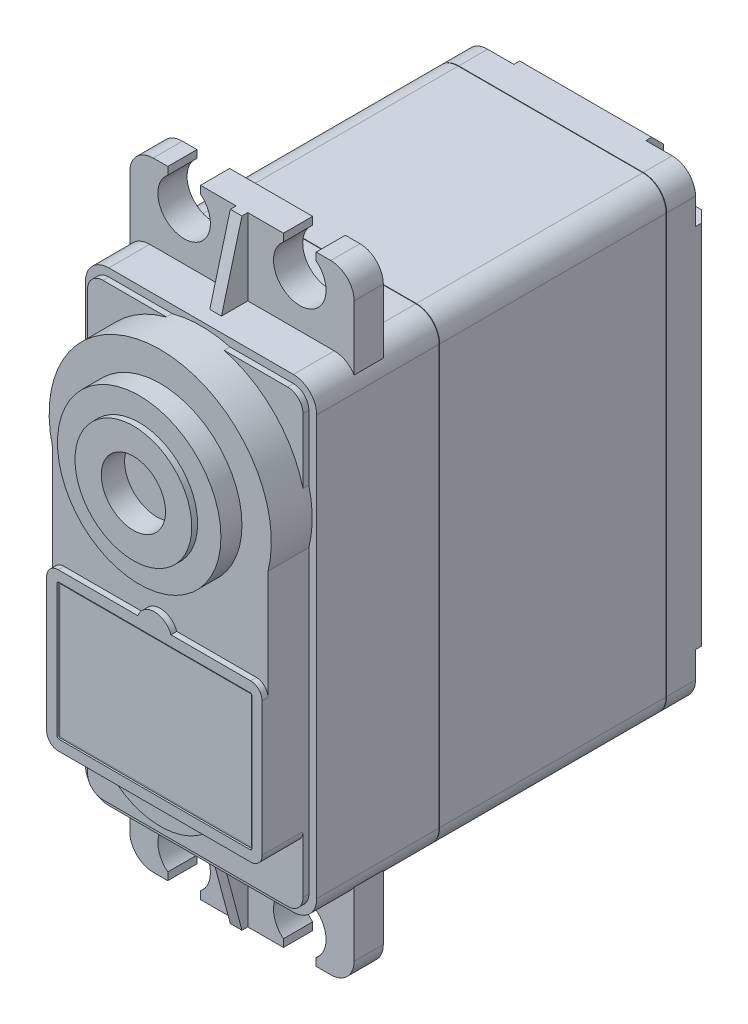
SolidWorks part; units mm, degrees
ref_plane "Piano frontale" through (0, 0, 0) normal (0, 0, 1) x (1, 0, 0)
ref_plane "Piano superiore" through (0, 0, 0) normal (0, 1, 0) x (1, 0, 0)
ref_plane "Piano destro" through (0, 0, 0) normal (1, 0, 0) x (0, 0, -1)
sketch "RIFERIMENTO" plane through (0, 0, 0) normal (0, 0, 1) x (1, 0, 0)
  line L0 (27.4785, 59.5052) -> (56.14, 59.5052) construction
  line L1 (31.8933, 83.5052) -> (51.7033, 83.5052) construction
  line L2 (31.8933, 35.5052) -> (51.7033, 35.5052) construction
  line L3 (41.7983, 33.0902) -> (41.7983, 85.9202) construction
  line L4 (46.7513, 33.0902) -> (46.7513, 85.9202) construction
  line L5 (36.8453, 33.0902) -> (36.8453, 85.9202) construction
  line L6 (35.4453, 33.0902) -> (35.4453, 33.7438)
  line L7 (38.2453, 33.0902) -> (38.2453, 33.7438)
  line L8 (45.3513, 33.0902) -> (45.3513, 33.7438)
  line L9 (48.1513, 33.0902) -> (48.1513, 33.7438)
  line L10 (38.2453, 33.0902) -> (45.3513, 33.0902)
  line L11 (35.4453, 85.9202) -> (35.4453, 85.2666)
  line L12 (38.2453, 85.9202) -> (38.2453, 85.2666)
  line L13 (48.1513, 85.9202) -> (48.1513, 85.2666)
  line L14 (45.3513, 85.9202) -> (45.3513, 85.2666)
  line L15 (35.4453, 85.9202) -> (34.1933, 85.9202)
  line L16 (32.1933, 83.9202) -> (32.1933, 78.4238)
  line L17 (45.3513, 85.9202) -> (38.2453, 85.9202)
  line L18 (28.408, 69.5052) -> (54.9221, 69.5052) construction
  line L19 (33.9696, 46.7742) -> (33.9696, 57.4156)
  line L20 (49.6489, 46.7742) -> (49.6489, 57.4156)
  line L21 (33.9696, 57.4156) -> (49.6489, 57.4156)
  line L22 (33.9696, 46.7742) -> (49.6489, 46.7742)
  line L23 (51.4033, 78.4238) -> (51.4033, 83.9202)
  line L24 (49.4033, 85.9202) -> (48.1513, 85.9202)
  line L25 (35.4453, 33.0902) -> (34.1933, 33.0902)
  line L26 (32.1933, 35.0902) -> (32.1933, 40.4366)
  line L27 (51.4033, 40.4366) -> (51.4033, 35.0902)
  line L28 (49.4033, 33.0902) -> (48.1513, 33.0902)
  line L29 (32.5696, 46.3742) -> (32.5696, 57.8156)
  line L30 (33.5696, 58.8156) -> (40.384, 58.8156)
  line L31 (33.5696, 45.3742) -> (50.0489, 45.3742)
  line L32 (42.3983, 69.2052) -> (42.6983, 69.2052)
  line L33 (42.8483, 69.3552) -> (42.8483, 69.6552)
  line L34 (42.6983, 69.8052) -> (42.3983, 69.8052)
  line L35 (42.0983, 70.1052) -> (42.0983, 70.4052)
  line L36 (41.9483, 70.5552) -> (41.6483, 70.5552)
  line L37 (41.4983, 70.4052) -> (41.4983, 70.1052)
  line L38 (41.1983, 69.8052) -> (40.8983, 69.8052)
  line L39 (40.7483, 69.6552) -> (40.7483, 69.3552)
  line L40 (40.8983, 69.2052) -> (41.1983, 69.2052)
  line L41 (41.4983, 68.9052) -> (41.4983, 68.6052)
  line L42 (41.6483, 68.4552) -> (41.9483, 68.4552)
  line L43 (42.0983, 68.6052) -> (42.0983, 68.9052)
  line L44 (31.8933, 77.3702) -> (31.8933, 41.4902)
  line L45 (33.8933, 39.4902) -> (49.7033, 39.4902)
  line L46 (51.7033, 41.4902) -> (51.7033, 77.3702)
  line L47 (49.7033, 79.3702) -> (33.8933, 79.3702)
  line L48 (32.5696, 77.3702) -> (32.5696, 41.4902)
  line L49 (33.8933, 40.1665) -> (49.7033, 40.1665)
  line L50 (51.027, 41.4902) -> (51.027, 77.3702)
  line L51 (49.7033, 78.6939) -> (33.8933, 78.6939)
  line L52 (51.027, 46.3742) -> (51.027, 57.8156)
  line L53 (42.2983, 33.0902) -> (42.2983, 39.4902)
  line L54 (41.2983, 33.0902) -> (41.2983, 39.4902)
  line L55 (42.2983, 81.4885) -> (42.2983, 85.9202)
  line L56 (41.2983, 81.4996) -> (41.2983, 85.9202)
  line L57 (70.4217, 57.5059) -> (70.4217, 81.4996)
  line L58 (70.4217, 81.4996) -> (72.4217, 81.4996)
  line L59 (72.4217, 81.4996) -> (72.4217, 57.5059)
  line L60 (72.4217, 57.5059) -> (70.4217, 57.5059)
  line L61 (76.9317, 45.3742) -> (76.9317, 58.8156)
  line L62 (76.9317, 58.8156) -> (77.4317, 58.8156)
  line L63 (80.9317, 39.4902) -> (80.9317, 79.3702)
  line L64 (113.8717, 39.4902) -> (80.9317, 39.4902)
  line L65 (91.4317, 39.4902) -> (91.4317, 79.3702)
  line L66 (80.9317, 79.3702) -> (113.8717, 79.3702)
  line L67 (114.8717, 78.3702) -> (114.8717, 40.4902)
  line L68 (86.9317, 39.4902) -> (86.9317, 33.0902)
  line L69 (86.9317, 33.0902) -> (84.4317, 33.0902)
  line L70 (84.4317, 33.0902) -> (84.4317, 39.4902)
  line L71 (84.4317, 33.0902) -> (83.9317, 33.0902)
  line L72 (83.9317, 33.0902) -> (82.2168, 39.4902)
  line L73 (86.9317, 79.3702) -> (86.9317, 85.7702)
  line L74 (86.9317, 85.7702) -> (84.4317, 85.7702)
  line L75 (84.4317, 85.7702) -> (84.4317, 79.3702)
  line L76 (84.4317, 85.7702) -> (83.9317, 85.7702)
  line L77 (83.9317, 85.7702) -> (82.2168, 79.3702)
  line L78 (76.9317, 45.3742) -> (80.4317, 45.3742)
  line L79 (80.9317, 78.8702) -> (80.4317, 78.8702)
  line L80 (77.4317, 79.0202) -> (77.4317, 58.8156)
  line L81 (76.9317, 58.8156) -> (76.9317, 59.8156)
  line L82 (76.9317, 59.8156) -> (77.4317, 59.8156)
  line L83 (77.4317, 43.6525) -> (80.4317, 43.6525)
  line L84 (80.9317, 39.9902) -> (80.4317, 39.9902)
  line L85 (80.4317, 39.9902) -> (80.4317, 67.1884)
  line L86 (77.4317, 45.3742) -> (77.4317, 43.6525)
  line L87 (80.9317, 79.0202) -> (77.4317, 79.0202)
  line L88 (77.4317, 67.1884) -> (80.4317, 67.1884)
  line L89 (80.4317, 71.8219) -> (80.4317, 78.8702)
  line L90 (69.9217, 65.8051) -> (69.9217, 73.2003)
  line L91 (70.4217, 73.2003) -> (69.9217, 73.2003)
  line L92 (70.4217, 65.8051) -> (69.9217, 65.8051)
  line L93 (110.8717, 79.3702) -> (110.8717, 39.4902)
  line L94 (114.8717, 43.7402) -> (113.3717, 43.7402)
  line L95 (113.3717, 43.7402) -> (113.3717, 39.4902)
  line L96 (113.8717, 39.4902) -> (114.8717, 40.4902)
  line L97 (113.8717, 79.3702) -> (114.8717, 78.3702)
  line L98 (114.8717, 75.1202) -> (113.3717, 75.1202)
  line L99 (113.3717, 75.1202) -> (113.3717, 79.3702)
  line L100 (113.8717, 75.1202) -> (113.8717, 43.7402)
  line L101 (72.4217, 74.0027) -> (74.4217, 74.0027)
  line L102 (74.4217, 74.0027) -> (74.4217, 65.0027)
  line L103 (74.4217, 65.0027) -> (72.4217, 65.0027)
  line L104 (67.8152, 69.5052) -> (83.0318, 69.5052) construction
  line L105 (75.6317, 76.5052) -> (75.6317, 62.5052)
  line L106 (75.6317, 76.5052) -> (77.4317, 76.5052)
  line L107 (75.6317, 62.5052) -> (77.4317, 62.5052)
  line L108 (75.6317, 74.5052) -> (75.1317, 74.5052)
  line L109 (75.1317, 74.5052) -> (75.1317, 64.5052)
  line L110 (75.1317, 64.5052) -> (75.6317, 64.5052)
  line L111 (43.2125, 58.8156) -> (50.0489, 58.8156)
  arc A0 (48.1513, 33.7438) -> (45.3513, 33.7438) centre (46.7513, 35.5052) ccw
  arc A1 (38.2453, 33.7438) -> (35.4453, 33.7438) centre (36.8453, 35.5052) ccw
  arc A2 (35.4453, 85.2666) -> (38.2453, 85.2666) centre (36.8453, 83.5052) ccw
  arc A3 (45.3513, 85.2666) -> (48.1513, 85.2666) centre (46.7513, 83.5052) ccw
  circle A4 centre (41.6651, 69.5052) radius 12
  circle A5 centre (50.2983, 69.5052) radius 0.6
  circle A6 centre (49.7985, 72.3768) radius 0.6
  circle A7 centre (49.7985, 66.6335) radius 0.6
  circle A8 centre (33.2983, 69.5052) radius 0.6
  circle A9 centre (33.798, 72.3768) radius 0.6
  circle A10 centre (33.798, 66.6335) radius 0.6
  circle A11 centre (41.7983, 76.3052) radius 0.6
  circle A12 centre (41.7983, 79.5052) radius 0.6
  circle A13 centre (44.1459, 75.8871) radius 0.6
  circle A14 centre (45.2506, 78.8903) radius 0.6
  circle A15 centre (39.4507, 75.8871) radius 0.6
  circle A16 centre (38.3459, 78.8903) radius 0.6
  circle A17 centre (41.7983, 62.7052) radius 0.6
  circle A18 centre (41.7983, 59.5052) radius 0.6
  circle A19 centre (44.1459, 63.1233) radius 0.6
  circle A20 centre (45.2506, 60.12) radius 0.6
  circle A21 centre (39.4507, 63.1233) radius 0.6
  circle A22 centre (38.3459, 60.12) radius 0.6
  circle A23 centre (41.7983, 69.5052) radius 2.5
  circle A24 centre (41.7983, 69.5052) radius 2.9
  circle A25 centre (41.7983, 69.5052) radius 3.7
  arc A26 (32.5696, 46.3742) -> (33.5696, 45.3742) centre (33.5696, 46.3742) ccw
  arc A27 (33.5696, 58.8156) -> (32.5696, 57.8156) centre (33.5696, 57.8156) ccw
  arc A28 (37.6025, 45.3742) -> (46.0159, 45.3742) centre (41.8092, 49.6525) ccw
  arc A29 (50.027, 45.3742) -> (51.027, 46.3742) centre (50.027, 46.3742) ccw
  arc A30 (51.027, 57.8156) -> (50.027, 58.8156) centre (50.027, 57.8156) ccw
  arc A31 (43.2125, 58.8156) -> (40.384, 58.8156) centre (41.7983, 58.3156) ccw
  arc A32 (34.1933, 85.9202) -> (32.1933, 83.9202) centre (34.1933, 83.9202) ccw
  arc A33 (51.4033, 83.9202) -> (49.4033, 85.9202) centre (49.4033, 83.9202) ccw
  arc A34 (32.1933, 35.0902) -> (34.1933, 33.0902) centre (34.1933, 35.0902) ccw
  arc A35 (49.4033, 33.0902) -> (51.4033, 35.0902) centre (49.4033, 35.0902) ccw
  arc A36 (42.3983, 69.2052) -> (42.0983, 68.9052) centre (42.3983, 68.9052) ccw
  arc A37 (42.6983, 69.2052) -> (42.8483, 69.3552) centre (42.6983, 69.3552) ccw
  arc A38 (42.8483, 69.6552) -> (42.6983, 69.8052) centre (42.6983, 69.6552) ccw
  arc A39 (42.0983, 70.1052) -> (42.3983, 69.8052) centre (42.3983, 70.1052) ccw
  arc A40 (42.0983, 70.4052) -> (41.9483, 70.5552) centre (41.9483, 70.4052) ccw
  arc A41 (41.6483, 70.5552) -> (41.4983, 70.4052) centre (41.6483, 70.4052) ccw
  arc A42 (41.1983, 69.8052) -> (41.4983, 70.1052) centre (41.1983, 70.1052) ccw
  arc A43 (40.8983, 69.8052) -> (40.7483, 69.6552) centre (40.8983, 69.6552) ccw
  arc A44 (40.7483, 69.3552) -> (40.8983, 69.2052) centre (40.8983, 69.3552) ccw
  arc A45 (41.4983, 68.9052) -> (41.1983, 69.2052) centre (41.1983, 68.9052) ccw
  arc A46 (41.4983, 68.6052) -> (41.6483, 68.4552) centre (41.6483, 68.6052) ccw
  arc A47 (41.9483, 68.4552) -> (42.0983, 68.6052) centre (41.9483, 68.6052) ccw
  arc A48 (31.8933, 41.4902) -> (33.8933, 39.4902) centre (33.8933, 41.4902) ccw
  arc A49 (49.7033, 39.4902) -> (51.7033, 41.4902) centre (49.7033, 41.4902) ccw
  arc A50 (51.7033, 77.3702) -> (49.7033, 79.3702) centre (49.7033, 77.3702) ccw
  arc A51 (33.8933, 79.3702) -> (31.8933, 77.3702) centre (33.8933, 77.3702) ccw
  arc A52 (32.5696, 41.4902) -> (33.8933, 40.1665) centre (33.8933, 41.4902) ccw
  arc A53 (49.7033, 40.1665) -> (51.027, 41.4902) centre (49.7033, 41.4902) ccw
  arc A54 (51.027, 77.3702) -> (49.7033, 78.6939) centre (49.7033, 77.3702) ccw
  arc A55 (33.8933, 78.6939) -> (32.5696, 77.3702) centre (33.8933, 77.3702) ccw
sketch "Schizzo2" plane through (0, 0, 0) normal (0, 0, 1) x (1, 0, 0)
  line L0 (49.7033, 79.3702) -> (33.8933, 79.3702) construction
  line L1 (51.7033, 41.4902) -> (51.7033, 77.3702) construction
  line L2 (33.8933, 39.4902) -> (49.7033, 39.4902) construction
  line L3 (31.8933, 77.3702) -> (31.8933, 41.4902) construction
  line L4 (49.7033, 79.3702) -> (33.8933, 79.3702)
  line L5 (51.7033, 41.4902) -> (51.7033, 77.3702)
  line L6 (33.8933, 39.4902) -> (49.7033, 39.4902)
  line L7 (31.8933, 77.3702) -> (31.8933, 41.4902)
  arc A0 (33.8933, 79.3702) -> (31.8933, 77.3702) centre (33.8933, 77.3702) ccw construction
  arc A1 (51.7033, 77.3702) -> (49.7033, 79.3702) centre (49.7033, 77.3702) ccw construction
  arc A2 (49.7033, 39.4902) -> (51.7033, 41.4902) centre (49.7033, 41.4902) ccw construction
  arc A3 (31.8933, 41.4902) -> (33.8933, 39.4902) centre (33.8933, 41.4902) ccw construction
  arc A4 (33.8933, 79.3702) -> (31.8933, 77.3702) centre (33.8933, 77.3702) ccw
  arc A5 (51.7033, 77.3702) -> (49.7033, 79.3702) centre (49.7033, 77.3702) ccw
  arc A6 (49.7033, 39.4902) -> (51.7033, 41.4902) centre (49.7033, 41.4902) ccw
  arc A7 (31.8933, 41.4902) -> (33.8933, 39.4902) centre (33.8933, 41.4902) ccw
extrude "Estrusione-Estrusione1" add sketch "Schizzo2" along normal blind 4
sketch "Schizzo3" plane through (0, 0, 4) normal (0, 0, 1) x (1, 0, 0)
  line L4 (31.8933, 77.3702) -> (31.8933, 41.4902)
  line L5 (33.8933, 39.4902) -> (49.7033, 39.4902)
  line L6 (51.7033, 41.4902) -> (51.7033, 77.3702)
  line L7 (49.7033, 79.3702) -> (33.8933, 79.3702)
  line L8 (31.8933, 77.3702) -> (31.8933, 41.4902)
  line L9 (33.8933, 39.4902) -> (49.7033, 39.4902)
  line L10 (51.7033, 41.4902) -> (51.7033, 77.3702)
  line L11 (49.7033, 79.3702) -> (33.8933, 79.3702)
  arc A4 (33.8933, 79.3702) -> (31.8933, 77.3702) centre (33.8933, 77.3702) ccw
  arc A5 (31.8933, 41.4902) -> (33.8933, 39.4902) centre (33.8933, 41.4902) ccw
  arc A6 (49.7033, 39.4902) -> (51.7033, 41.4902) centre (49.7033, 41.4902) ccw
  arc A7 (51.7033, 77.3702) -> (49.7033, 79.3702) centre (49.7033, 77.3702) ccw
  arc A8 (33.8933, 79.3702) -> (31.8933, 77.3702) centre (33.8933, 77.3702) ccw
  arc A9 (31.8933, 41.4902) -> (33.8933, 39.4902) centre (33.8933, 41.4902) ccw
  arc A10 (49.7033, 39.4902) -> (51.7033, 41.4902) centre (49.7033, 41.4902) ccw
  arc A11 (51.7033, 77.3702) -> (49.7033, 79.3702) centre (49.7033, 77.3702) ccw
  dimension "D1" = 0
extrude "Estrusione-Estrusione2" add sketch "Schizzo3" along normal blind 19.44 separate body
sketch "Schizzo4" plane through (0, 0, 23.44) normal (0, 0, 1) x (1, 0, 0)
  line L4 (31.8933, 77.3702) -> (31.8933, 41.4902)
  line L5 (33.8933, 39.4902) -> (49.7033, 39.4902)
  line L6 (51.7033, 41.4902) -> (51.7033, 77.3702)
  line L7 (49.7033, 79.3702) -> (33.8933, 79.3702)
  line L8 (31.8933, 77.3702) -> (31.8933, 41.4902)
  line L9 (33.8933, 39.4902) -> (49.7033, 39.4902)
  line L10 (51.7033, 41.4902) -> (51.7033, 77.3702)
  line L11 (49.7033, 79.3702) -> (33.8933, 79.3702)
  arc A4 (33.8933, 79.3702) -> (31.8933, 77.3702) centre (33.8933, 77.3702) ccw
  arc A5 (31.8933, 41.4902) -> (33.8933, 39.4902) centre (33.8933, 41.4902) ccw
  arc A6 (49.7033, 39.4902) -> (51.7033, 41.4902) centre (49.7033, 41.4902) ccw
  arc A7 (51.7033, 77.3702) -> (49.7033, 79.3702) centre (49.7033, 77.3702) ccw
  arc A8 (33.8933, 79.3702) -> (31.8933, 77.3702) centre (33.8933, 77.3702) ccw
  arc A9 (31.8933, 41.4902) -> (33.8933, 39.4902) centre (33.8933, 41.4902) ccw
  arc A10 (49.7033, 39.4902) -> (51.7033, 41.4902) centre (49.7033, 41.4902) ccw
  arc A11 (51.7033, 77.3702) -> (49.7033, 79.3702) centre (49.7033, 77.3702) ccw
  dimension "D1" = 0
extrude "Estrusione-Estrusione3" add sketch "Schizzo4" along normal blind 10.5 separate body
ref_plane "Piano1" through (0, 0, 27.94) normal (0, 0, 1) x (1, 0, 0)
sketch "Schizzo5" plane through (0, 0, 27.94) normal (0, 0, 1) x (1, 0, 0)
  line L0 (32.1933, 83.9202) -> (32.1933, 78.4238) construction
  line L1 (35.4453, 85.9202) -> (34.1933, 85.9202) construction
  line L2 (45.3513, 85.9202) -> (38.2453, 85.9202) construction
  line L3 (49.4033, 85.9202) -> (48.1513, 85.9202) construction
  line L4 (51.4033, 78.4238) -> (51.4033, 83.9202) construction
  line L5 (35.4453, 85.9202) -> (35.4453, 85.2666) construction
  line L6 (38.2453, 85.9202) -> (38.2453, 85.2666) construction
  line L7 (45.3513, 85.9202) -> (45.3513, 85.2666) construction
  line L8 (48.1513, 85.9202) -> (48.1513, 85.2666) construction
  line L9 (49.7033, 79.3702) -> (33.8933, 79.3702) construction
  line L10 (32.1933, 83.9202) -> (32.1933, 78.4238)
  line L11 (35.4453, 85.9202) -> (34.1933, 85.9202)
  line L12 (45.3513, 85.9202) -> (38.2453, 85.9202)
  line L13 (49.4033, 85.9202) -> (48.1513, 85.9202)
  line L14 (51.4033, 78.4238) -> (51.4033, 83.9202)
  line L15 (35.4453, 85.9202) -> (35.4453, 85.2666)
  line L16 (38.2453, 85.9202) -> (38.2453, 85.2666)
  line L17 (45.3513, 85.9202) -> (45.3513, 85.2666)
  line L18 (48.1513, 85.9202) -> (48.1513, 85.2666)
  line L19 (49.7033, 79.3702) -> (33.8933, 79.3702)
  arc A0 (34.1933, 85.9202) -> (32.1933, 83.9202) centre (34.1933, 83.9202) ccw construction
  arc A1 (51.4033, 83.9202) -> (49.4033, 85.9202) centre (49.4033, 83.9202) ccw construction
  arc A2 (45.3513, 85.2666) -> (48.1513, 85.2666) centre (46.7513, 83.5052) ccw construction
  arc A3 (35.4453, 85.2666) -> (38.2453, 85.2666) centre (36.8453, 83.5052) ccw construction
  arc A4 (33.8933, 79.3702) -> (31.8933, 77.3702) centre (33.8933, 77.3702) ccw construction
  arc A5 (51.7033, 77.3702) -> (49.7033, 79.3702) centre (49.7033, 77.3702) ccw construction
  arc A6 (34.1933, 85.9202) -> (32.1933, 83.9202) centre (34.1933, 83.9202) ccw
  arc A7 (51.4033, 83.9202) -> (49.4033, 85.9202) centre (49.4033, 83.9202) ccw
  arc A8 (45.3513, 85.2666) -> (48.1513, 85.2666) centre (46.7513, 83.5052) ccw
  arc A9 (35.4453, 85.2666) -> (38.2453, 85.2666) centre (36.8453, 83.5052) ccw
  arc A10 (33.8933, 79.3702) -> (32.1933, 78.4238) centre (33.8933, 77.3702) ccw
  arc A11 (51.4033, 78.4238) -> (49.7033, 79.3702) centre (49.7033, 77.3702) ccw
extrude "Estrusione-Estrusione4" add sketch "Schizzo5" along normal blind 2.5 separate body
ref_plane "Piano di Mezzeria TRASVERSALE" through (0, 59.4302, 0) normal (0, 1, 0) x (-1, 0, 0)
ref_plane "Piano di Mezzeria LONGITUDINALE" through (41.7983, 0, 0) normal (1, 0, 0) x (0, 0, -1)
sketch "Schizzo7" plane through (41.7983, 0, 0) normal (1, 0, 0) x (0, 0, -1)
  line L0 (-30.44, 85.9202) -> (-30.94, 85.9202)
  line L1 (-30.94, 85.9202) -> (-32.6951, 79.3702)
  line L2 (-33.94, 79.3702) -> (-23.44, 79.3702) construction
  line L3 (-32.6951, 79.3702) -> (-30.44, 79.3702)
  line L4 (-30.44, 79.3702) -> (-30.44, 85.9202)
  dimension "D1" = 15
  dimension "D2" = 0.5
extrude "Estrusione-Estrusione5" add sketch "Schizzo7" along normal mid plane 1 separate body
mirror "Specchia1" about plane through (0, 59.4302, 0) normal (0, 1, 0) of bodies 104 105
combine bodies "Abbina1" operation type add bodies to combine 107 106 103 104 105
sketch "Schizzo8" plane through (51.7033, 0, 0) normal (1, 0, 0) x (0, 0, -1)
  line L2 (-4, 75.1202) -> (0, 75.1202)
  line L3 (-1.5, 75.1202) -> (1.0182, 75.1202)
  line L4 (-1.5, 80.472) -> (1.0182, 80.472)
  line L5 (-1.5, 41.4902) -> (-1.5, 77.3702)
  line L6 (-1.5, 75.1202) -> (-1.5, 80.472)
  line L7 (1.0182, 80.472) -> (1.0182, 75.1202)
  line L8 (-6.4413, 59.4302) -> (5.8059, 59.4302) construction
  line L9 (1.0182, 38.3884) -> (1.0182, 43.7402)
  line L10 (-1.5, 43.7402) -> (-1.5, 38.3884)
  line L11 (-1.5, 38.3884) -> (1.0182, 38.3884)
  line L12 (-1.5, 43.7402) -> (1.0182, 43.7402)
  dimension "D1" = 4.25
  dimension "D2" = 1.5
extrude "Taglio-Estrusione1" cut sketch "Schizzo8" against normal blind 4.25
mirror "Specchia2" about plane through (41.7983, 0, 0) normal (1, 0, 0) of "Taglio-Estrusione1"
fillet "Raccordo1" radius 2.5 4 edges at (47.4533, 43.7402, 0.75) (36.1433, 43.7402, 0.75) (36.1433, 75.1202, 0.75) (47.4533, 75.1202, 0.75)
chamfer "Smusso1" distance 1 angle 45 4 edges at (41.7983, 79.3702, 0) (31.8933, 59.4302, 0) (51.7033, 59.4302, 0) (41.7983, 39.4902, 0)
sketch "Schizzo9" plane through (0, 0, 33.94) normal (0, 0, 1) x (1, 0, 0)
  line L0 (32.5696, 77.3702) -> (32.5696, 41.4902) construction
  line L1 (49.7033, 78.6939) -> (33.8933, 78.6939) construction
  line L2 (51.027, 41.4902) -> (51.027, 77.3702) construction
  line L3 (33.8933, 40.1665) -> (49.7033, 40.1665) construction
  line L4 (32.5696, 77.3702) -> (32.5696, 41.4902)
  line L5 (49.7033, 78.6939) -> (33.8933, 78.6939)
  line L6 (51.027, 41.4902) -> (51.027, 77.3702)
  line L7 (33.8933, 40.1665) -> (49.7033, 40.1665)
  arc A0 (33.8933, 78.6939) -> (32.5696, 77.3702) centre (33.8933, 77.3702) ccw construction
  arc A1 (51.027, 77.3702) -> (49.7033, 78.6939) centre (49.7033, 77.3702) ccw construction
  arc A2 (49.7033, 40.1665) -> (51.027, 41.4902) centre (49.7033, 41.4902) ccw construction
  arc A3 (32.5696, 41.4902) -> (33.8933, 40.1665) centre (33.8933, 41.4902) ccw construction
  arc A4 (33.8933, 78.6939) -> (32.5696, 77.3702) centre (33.8933, 77.3702) ccw
  arc A5 (51.027, 77.3702) -> (49.7033, 78.6939) centre (49.7033, 77.3702) ccw
  arc A6 (49.7033, 40.1665) -> (51.027, 41.4902) centre (49.7033, 41.4902) ccw
  arc A7 (32.5696, 41.4902) -> (33.8933, 40.1665) centre (33.8933, 41.4902) ccw
extrude "Estrusione-Estrusione6" add sketch "Schizzo9" along normal blind 0.5
sketch "Schizzo10" plane through (0, 0, 34.44) normal (0, 0, 1) x (1, 0, 0)
  line L0 (33.5696, 45.3742) -> (50.0489, 45.3742) construction
  line L2 (33.5696, 45.3742) -> (37.6025, 45.3742)
  line L7 (46.0159, 45.3742) -> (50.0489, 45.3742)
  line L8 (32.5696, 67.1886) -> (32.5696, 46.3742)
  line L9 (51.027, 67.1886) -> (51.027, 46.3742)
  arc A0 (37.6025, 45.3742) -> (46.0159, 45.3742) centre (41.8092, 49.6525) ccw construction
  arc A1 (32.5696, 46.3742) -> (33.5696, 45.3742) centre (33.5696, 46.3742) ccw construction
  arc A2 (50.027, 45.3742) -> (51.027, 46.3742) centre (50.027, 46.3742) ccw construction
  arc A5 (37.6025, 45.3742) -> (46.0159, 45.3742) centre (41.8092, 49.6525) ccw
  arc A6 (32.5696, 46.3742) -> (33.5696, 45.3742) centre (33.5696, 46.3742) ccw
  arc A7 (50.027, 45.3742) -> (51.027, 46.3742) centre (50.027, 46.3742) ccw
  arc A10 (39.328, 78.6939) -> (32.5696, 67.1886) centre (41.7983, 69.5052) ccw
  arc A11 (51.027, 67.1886) -> (44.2685, 78.6939) centre (41.7983, 69.5052) ccw
  arc A12 (44.2685, 78.6939) -> (39.328, 78.6939) centre (41.7983, 69.5052) ccw
  arc M1 (33.8933, 78.6939) -> (32.5696, 77.3702) centre (33.8933, 77.3702) ccw
  line M2 (32.5696, 77.3702) -> (32.5696, 41.4902)
  line M6 (51.027, 41.4902) -> (51.027, 77.3702)
  arc M7 (51.027, 77.3702) -> (49.7033, 78.6939) centre (49.7033, 77.3702) ccw
  line M8 (49.7033, 78.6939) -> (33.8933, 78.6939)
  dimension "D1" = 9.515
extrude "Estrusione-Estrusione7" add sketch "Schizzo10" along normal blind 3 contours A12 M8 | A11 M6 | A10 M2 | L7 A7 A6 L2 A5 M6 M7 M8 M1 M2
sketch "Schizzo11" plane through (0, 0, 37.44) normal (0, 0, 1) x (1, 0, 0)
  line L0 (33.5696, 45.3742) -> (50.0489, 45.3742) construction
  line L1 (32.5696, 46.3742) -> (32.5696, 57.8156) construction
  line L2 (51.027, 41.4902) -> (51.027, 77.3702) construction
  line L3 (33.5696, 58.8156) -> (40.384, 58.8156) construction
  line L4 (43.2125, 58.8156) -> (50.0489, 58.8156) construction
  line L5 (33.5696, 45.3742) -> (50.0489, 45.3742)
  line L6 (32.5696, 46.3742) -> (32.5696, 57.8156)
  line L7 (51.027, 46.3742) -> (51.027, 57.8156)
  line L8 (33.5696, 58.8156) -> (40.384, 58.8156)
  line L9 (43.2125, 58.8156) -> (50.0489, 58.8156)
  arc A0 (32.5696, 46.3742) -> (33.5696, 45.3742) centre (33.5696, 46.3742) ccw construction
  arc A1 (50.027, 45.3742) -> (51.027, 46.3742) centre (50.027, 46.3742) ccw construction
  arc A2 (33.5696, 58.8156) -> (32.5696, 57.8156) centre (33.5696, 57.8156) ccw construction
  arc A3 (51.027, 57.8156) -> (50.027, 58.8156) centre (50.027, 57.8156) ccw construction
  arc A4 (43.2125, 58.8156) -> (40.384, 58.8156) centre (41.7983, 58.3156) ccw construction
  arc A5 (32.5696, 46.3742) -> (33.5696, 45.3742) centre (33.5696, 46.3742) ccw
  arc A6 (50.027, 45.3742) -> (51.027, 46.3742) centre (50.027, 46.3742) ccw
  arc A7 (33.5696, 58.8156) -> (32.5696, 57.8156) centre (33.5696, 57.8156) ccw
  arc A8 (51.027, 57.8156) -> (50.027, 58.8156) centre (50.027, 57.8156) ccw
  arc A9 (43.2125, 58.8156) -> (40.384, 58.8156) centre (41.7983, 58.3156) ccw
  line M1 (46.0159, 45.3742) -> (50.027, 45.3742)
  arc M2 (50.027, 45.3742) -> (51.027, 46.3742) centre (50.027, 46.3742) ccw
  line M3 (51.027, 46.3742) -> (51.027, 67.1886)
  line M9 (32.5696, 67.1886) -> (32.5696, 46.3742)
  arc M10 (32.5696, 46.3742) -> (33.5696, 45.3742) centre (33.5696, 46.3742) ccw
  line M11 (33.5696, 45.3742) -> (37.6025, 45.3742)
extrude "Estrusione-Estrusione8" add sketch "Schizzo11" along normal blind 0.5 contours L9 A9 L8 A7 L5 A8 M9 M10 M11 M1 M2 M3
sketch "Schizzo12" plane through (0, 0, 33.94) normal (0, 0, 1) x (1, 0, 0)
  circle A0 centre (41.7983, 69.5052) radius 9.515
extrude "Estrusione-Estrusione9" add sketch "Schizzo12" along normal blind 0.5
sketch "Schizzo13" plane through (0, 0, 37.94) normal (0, 0, 1) x (1, 0, 0)
  line L13 (50.1489, 46.2742) -> (50.1489, 57.9156)
  line L14 (33.4696, 46.2742) -> (50.1489, 46.2742)
  line L15 (33.4696, 57.9156) -> (33.4696, 46.2742)
  line L16 (50.1489, 57.9156) -> (33.4696, 57.9156)
  line L17 (50.1489, 46.4242) -> (50.1489, 57.7656)
  line L18 (33.6196, 46.2742) -> (49.9989, 46.2742)
  line L19 (33.4696, 57.7656) -> (33.4696, 46.4242)
  line L20 (49.9989, 57.9156) -> (33.6196, 57.9156)
  arc A5 (33.6196, 46.2742) -> (33.4696, 46.4242) centre (33.6196, 46.4242) cw
  arc A6 (50.1489, 46.4242) -> (49.9989, 46.2742) centre (49.9989, 46.4242) cw
  arc A7 (50.1489, 57.7656) -> (49.9989, 57.9156) centre (49.9989, 57.7656) ccw
  arc A8 (33.4696, 57.7656) -> (33.6196, 57.9156) centre (33.6196, 57.7656) cw
  dimension "D2" = 0.15
  dimension "D1" = 0.5
extrude "Taglio-Estrusione2" cut sketch "Schizzo13" against normal blind 0.15
sketch "Schizzo14" plane through (0, 0, 37.44) normal (0, 0, 1) x (1, 0, 0)
  circle A0 centre (41.7983, 69.5052) radius 7
  dimension "D1" = 14
extrude "Estrusione-Estrusione10" add sketch "Schizzo14" along normal blind 1.8
sketch "Schizzo15" plane through (0, 0, 39.24) normal (0, 0, 1) x (1, 0, 0)
  circle A0 centre (41.7983, 69.5052) radius 5
  dimension "D1" = 10
extrude "Estrusione-Estrusione11" add sketch "Schizzo15" along normal blind 0.5
sketch "Schizzo16" plane through (0, 0, 39.74) normal (0, 0, 1) x (1, 0, 0)
  circle A0 centre (41.7983, 69.5052) radius 2.75
  dimension "D1" = 5.5
extrude "Taglio-Estrusione3" cut sketch "Schizzo16" against normal blind 2
sketch "Schizzo17" plane through (0, 0, 37.79) normal (0, 0, 1) x (1, 0, 0)
  line L8 (33.6196, 46.4242) -> (49.9989, 46.4242)
  line L9 (49.9989, 46.4242) -> (49.9989, 57.7656)
  line L10 (49.9989, 57.7656) -> (33.6196, 57.7656)
  line L11 (33.6196, 57.7656) -> (33.6196, 46.4242)
  line L12 (33.6196, 46.4242) -> (49.9989, 46.4242)
  line L13 (49.9989, 46.4242) -> (49.9989, 57.7656)
  line L14 (49.9989, 57.7656) -> (33.6196, 57.7656)
  line L15 (33.6196, 57.7656) -> (33.6196, 46.4242)
  dimension "D1" = 0.15
extrude "Estrusione-Estrusione12" add sketch "Schizzo17" along normal blind 0.05 separate body
chamfer "Smusso2" distance 0.025 angle 60 8 edges at (51.7033, 59.4302, 4) (51.1175, 78.7844, 4) (51.1175, 40.076, 4) (41.7983, 79.3702, 4) (41.7983, 39.4902, 4) (32.479, 78.7844, 4) (32.479, 40.076, 4) (31.8933, 59.4302, 4)
chamfer "Smusso3" distance 0.025 angle 30 8 edges at (51.7033, 59.4302, 4) (51.1175, 78.7844, 4) (51.1175, 40.076, 4) (41.7983, 79.3702, 4) (41.7983, 39.4902, 4) (32.479, 78.7844, 4) (32.479, 40.076, 4) (31.8933, 59.4302, 4)
chamfer "Smusso4" distance 0.025 angle 30 8 edges at (51.7033, 59.4302, 23.44) (51.1175, 78.7844, 23.44) (51.1175, 40.076, 23.44) (41.7983, 79.3702, 23.44) (41.7983, 39.4902, 23.44) (32.479, 78.7844, 23.44) (32.479, 40.076, 23.44) (31.8933, 59.4302, 23.44)
chamfer "Smusso5" distance 0.025 angle 60 8 edges at (51.7033, 59.4302, 23.44) (51.1175, 78.7844, 23.44) (51.1175, 40.076, 23.44) (41.7983, 79.3702, 23.44) (41.7983, 39.4902, 23.44) (32.479, 78.7844, 23.44) (32.479, 40.076, 23.44) (31.8933, 59.4302, 23.44)
